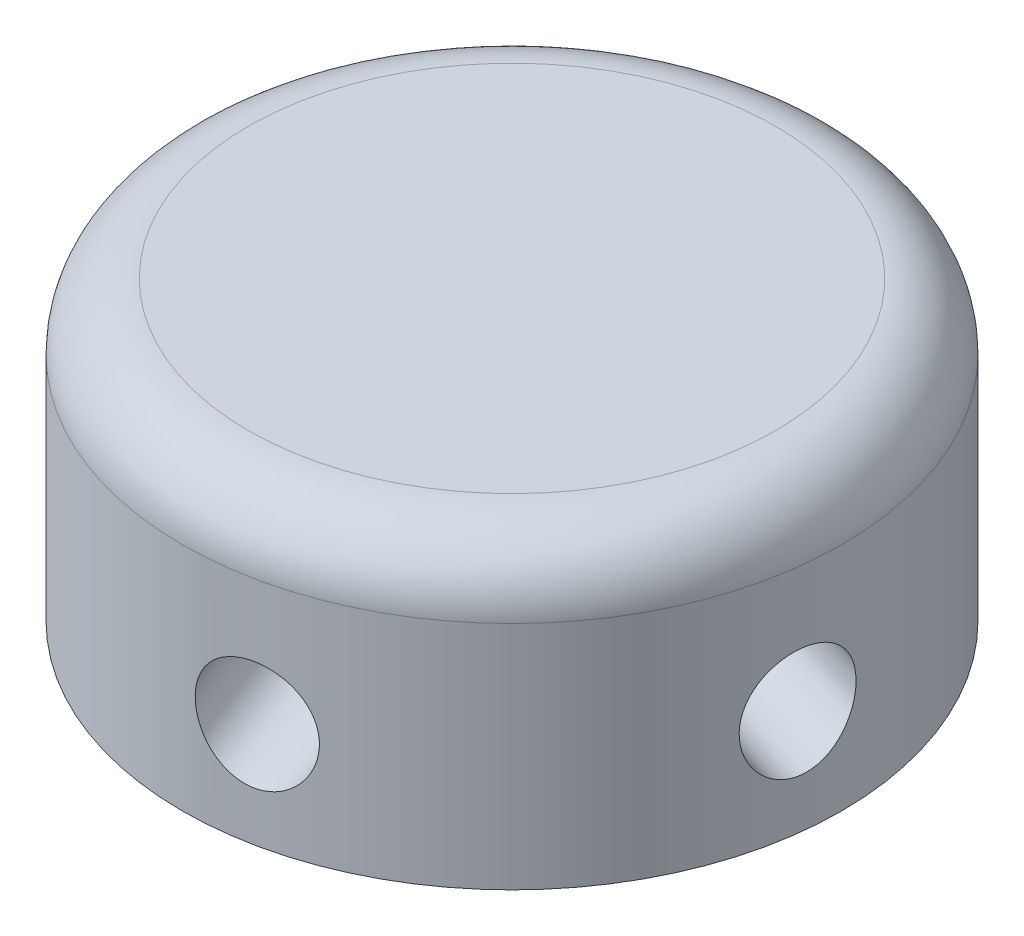
SolidWorks part; units mm, degrees
ref_plane "Front Plane" through (0, 0, 0) normal (0, 0, 1) x (1, 0, 0)
ref_plane "Top Plane" through (0, 0, 0) normal (0, 1, 0) x (1, 0, 0)
ref_plane "Right Plane" through (0, 0, 0) normal (1, 0, 0) x (0, 0, -1)
sketch "Sketch1" plane through (0, 0, 0) normal (0, 1, 0) x (1, 0, 0)
  circle A0 centre (0, 0) radius 10
  dimension "D1" = 20
extrude "Boss-Extrude1" add sketch "Sketch1" along normal blind 3 and the other way blind 6
ref_axis "5hubaxis" through (0, 5.5, 0) along (0, -1, 0)
ref_plane "holeplane" through (-3.3529, -1.0931, 1.8877) normal (0.8382, 0.2733, -0.4719) x (-0.4487, -0.1463, -0.8816)
sketch "Sketch4" plane through (-3.3529, -1.0931, 1.8877) normal (0.8382, 0.2733, -0.4719) x (-0.4487, -0.1463, -0.8816)
  circle A0 centre (0, 0) radius 1.5 construction
  circle A1 centre (0, 0) radius 1.5 construction
  circle A2 centre (0, 0) radius 1.6
  dimension "D1" = 3.2
extrude "hole" cut sketch "Sketch4" against normal through all
pattern_circular "holecir" count 5 over 360 about axis through (0, 5.5, 0) along (0, -1, 0) of "hole"
fillet "Fillet3" radius 2 1 edges at (0, 3, 10)
